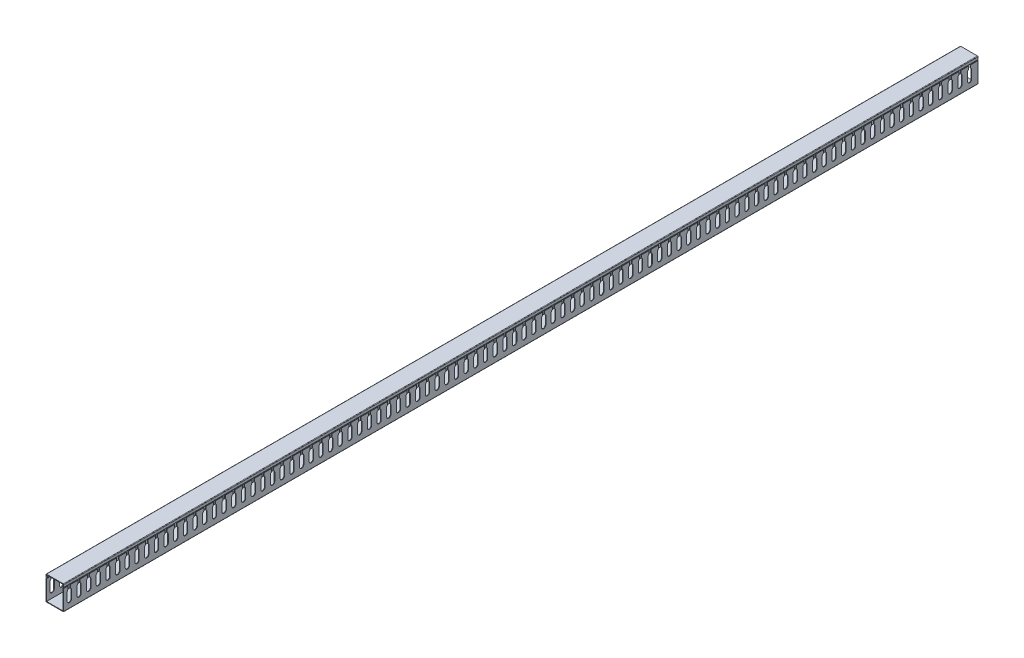
SolidWorks part; units mm, degrees
ref_plane "Front Plane" through (0, 0, 0) normal (0, 0, 1) x (1, 0, 0)
ref_plane "Top Plane" through (0, 0, 0) normal (0, 1, 0) x (1, 0, 0)
ref_plane "Right Plane" through (0, 0, 0) normal (1, 0, 0) x (0, 0, -1)
sketch "Sketch3" plane through (0, 0, 0) normal (0, 0, 1) x (1, 0, 0)
  line L234 (16.5, 37.8346) -> (16.5, 1)
  line L235 (16.3339, 38.3865) -> (14.281, 41.4887)
  line L236 (14.281, 41.4887) -> (15.5, 41.4887)
  line L237 (16.5, 39.6228) -> (16.5, 44)
  line L238 (16.5, 39.6228) -> (15.5158, 39.6228)
  line L239 (15.5, 41.4887) -> (15.5, 44)
  line L240 (15.5, 37.8346) -> (15.5, 1)
  line L241 (15.5, 37.8346) -> (13.5241, 40.8204)
  line L242 (13.6377, 42.0659) -> (15.5, 44)
  line L243 (-16.5, 37.8346) -> (-16.5, 1)
  line L244 (-16.3339, 38.3865) -> (-14.281, 41.4887)
  line L245 (-14.281, 41.4887) -> (-15.5, 41.4887)
  line L246 (-16.5, 39.6228) -> (-16.5, 44)
  line L247 (-16.5, 39.6228) -> (-15.5158, 39.6228)
  line L248 (-15.5, 41.4887) -> (-15.5, 44)
  line L249 (-15.5, 37.8346) -> (-15.5, 1)
  line L250 (-15.5, 37.8346) -> (-13.5241, 40.8204)
  line L251 (-13.6377, 42.0659) -> (-15.5, 44)
  line L252 (15.5, 0) -> (-15.5, 0)
  line L253 (15.5, 45) -> (-15.5, 45)
  line L254 (15.5, 1) -> (-15.5, 1)
  line L255 (15.5, 44) -> (-15.5, 44)
  arc A96 (16.5, 37.8346) -> (16.3339, 38.3865) centre (15.5, 37.8346) ccw
  arc A97 (13.6377, 42.0659) -> (13.5241, 40.8204) centre (14.358, 41.3723) ccw
  arc A98 (16.5, 44) -> (15.5, 45) centre (15.5, 44) ccw
  arc A99 (15.5, 0) -> (16.5, 1) centre (15.5, 1) ccw
  arc A100 (-16.3339, 38.3865) -> (-16.5, 37.8346) centre (-15.5, 37.8346) ccw
  arc A101 (-13.5241, 40.8204) -> (-13.6377, 42.0659) centre (-14.358, 41.3723) ccw
  arc A102 (-15.5, 45) -> (-16.5, 44) centre (-15.5, 44) ccw
  arc A103 (-16.5, 1) -> (-15.5, 0) centre (-15.5, 1) ccw
  point P7 (-109.4938, 10.5033)
sketch "Sketch4" plane through (0, 0, 0) normal (0, 0, 1) x (1, 0, 0)
  line L0 (-15.5, 37.8346) -> (-15.5, 1)
  line L1 (-15.5, 1) -> (15.5, 1)
  line L2 (15.5, 1) -> (15.5, 37.8346)
  line L3 (15.5, 37.8346) -> (15.5, 1) construction
  line L4 (15.5, 37.8346) -> (13.5241, 40.8204)
  line L5 (13.6377, 42.0659) -> (15.5, 44)
  line L6 (15.5, 44) -> (15.5, 41.4887)
  line L7 (15.5, 41.4887) -> (14.281, 41.4887)
  line L8 (14.281, 41.4887) -> (16.3339, 38.3865)
  line L9 (16.5, 37.8346) -> (16.5, 1)
  line L10 (15.5, 0) -> (-15.5, 0)
  line L11 (-16.5, 1) -> (-16.5, 37.8346)
  line L12 (-16.3339, 38.3865) -> (-14.281, 41.4887)
  line L13 (-14.281, 41.4887) -> (-15.5, 41.4887)
  line L14 (-15.5, 41.4887) -> (-15.5, 44)
  line L15 (-15.5, 44) -> (-13.6377, 42.0659)
  line L16 (-13.5241, 40.8204) -> (-15.5, 37.8346)
  line L17 (-15.5, 37.8346) -> (-15.5055, 37.8438)
  arc A0 (13.5241, 40.8204) -> (13.6377, 42.0659) centre (14.358, 41.3723) cw
  arc A1 (16.3339, 38.3865) -> (16.5, 37.8346) centre (15.5, 37.8346) cw
  arc A2 (16.5, 1) -> (15.5, 0) centre (15.5, 1) cw
  arc A3 (-15.5, 0) -> (-16.5, 1) centre (-15.5, 1) cw
  arc A4 (-16.5, 37.8346) -> (-16.3339, 38.3865) centre (-15.5, 37.8346) cw
  arc A5 (-13.6377, 42.0659) -> (-13.5241, 40.8204) centre (-14.358, 41.3723) cw
extrude "Boss-Extrude1" add sketch "Sketch4" along normal mid plane 1700
sketch "Sketch5" plane through (0, 0, 0) normal (0, 0, 1) x (1, 0, 0)
  line L0 (-14.281, 41.4887) -> (-15.5158, 39.6228)
  line L1 (-15.5158, 39.6228) -> (-16.5, 39.6228)
  line L2 (-16.5, 39.6228) -> (-16.5, 44)
  line L3 (-15.5, 45) -> (15.5, 45)
  line L4 (16.5, 44) -> (16.5, 39.6228)
  line L5 (16.5, 39.6228) -> (15.5158, 39.6228)
  line L6 (15.5158, 39.6228) -> (14.281, 41.4887)
  line L7 (14.281, 41.4887) -> (15.5, 41.4887)
  line L8 (15.5, 41.4887) -> (15.5, 44)
  line L9 (15.5, 44) -> (-15.5, 44)
  line L10 (-15.5, 44) -> (-15.5, 41.4887)
  line L11 (-15.5, 41.4887) -> (-14.281, 41.4887)
  arc A0 (-16.5, 44) -> (-15.5, 45) centre (-15.5, 44) cw
  arc A1 (15.5, 45) -> (16.5, 44) centre (15.5, 44) cw
extrude "Boss-Extrude2" add sketch "Sketch5" along normal mid plane 1700 separate body
sketch "Sketch6" plane through (16.5, 0, 0) normal (1, 0, 0) x (0, 0, -1)
  line L0 (-839.65, 29) -> (-839.65, 14) construction
  line L1 (-835.65, 29) -> (-835.65, 14)
  line L2 (-843.65, 29) -> (-843.65, 14)
  line L3 (-850, 0) -> (850, 0) construction
  line L4 (-850, 37.8346) -> (-850, 1) construction
  line L6 (-841.65, 44) -> (-837.65, 44)
  line L7 (-841.65, 44) -> (-841.65, 32.4641)
  line L9 (-837.65, 44) -> (-837.65, 32.4641)
  line L10 (-850, 44) -> (850, 44) construction
  arc A0 (-835.65, 29) -> (-837.65, 32.4641) centre (-839.65, 29) ccw
  arc A1 (-843.65, 14) -> (-835.65, 14) centre (-839.65, 14) ccw
  arc A2 (-841.65, 32.4641) -> (-843.65, 29) centre (-839.65, 29) ccw
  point P12 (-834.0251, 31.315)
  point P13 (-835.6689, 27.6307)
  point P15 (0, 0)
  point P16 (0, 0)
  point P19 (-837.765, 44)
  point P22 (-841.65, 32.1086)
  point P23 (0, 0)
  point P24 (0, 0)
  point P25 (-843.3464, 27.4714)
  point P26 (-843.65, 29)
  point P27 (0, 0)
  point P28 (0, 0)
  point P29 (-837.175, 29)
  point P30 (-837.65, 32.0334)
  point P31 (0, 0)
  point P32 (0, 0)
  point P33 (0, 0)
  point P34 (0, 0)
  point P35 (-838.3087, 23.1225)
  dimension "D4" = 4
  dimension "D1" = 15
  dimension "D2" = 14
  dimension "D3" = 10.35
  dimension "D5" = 4
  dimension "D6" = 2
extrude "Cut-Extrude1" cut sketch "Sketch6" against normal through all
pattern_linear "LPattern1" count 94 spacing 18 along (0, 0, -1) of "Cut-Extrude1"
